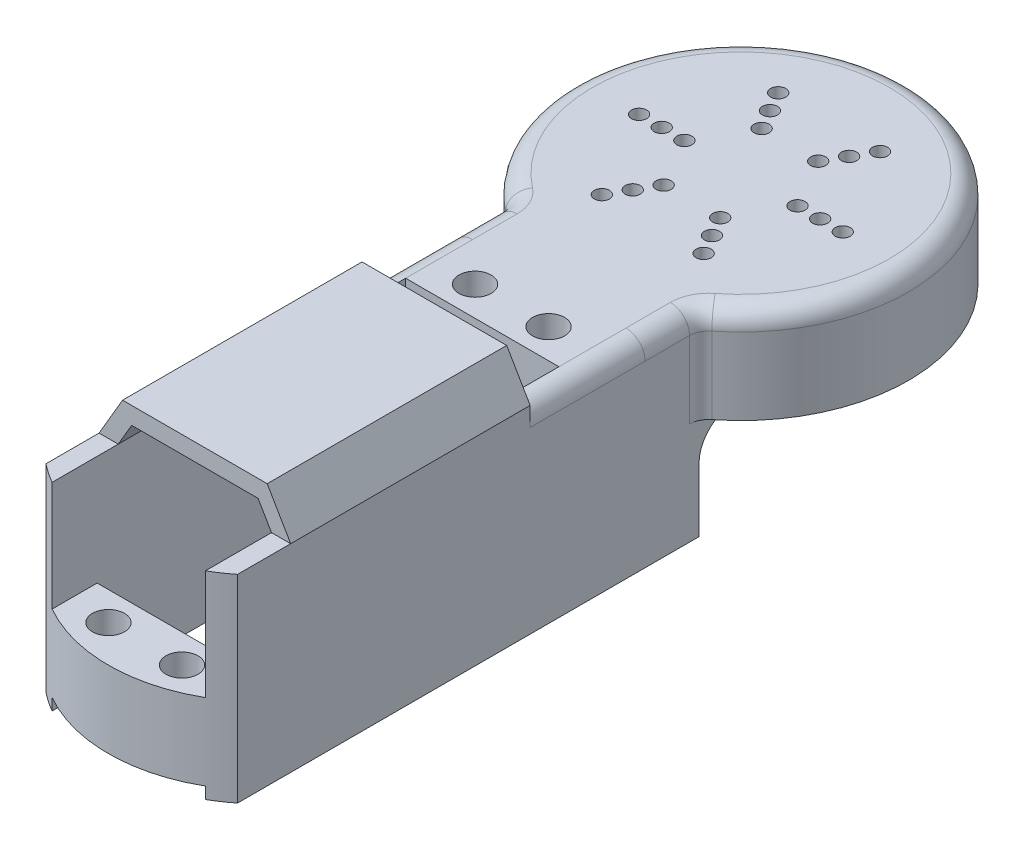
SolidWorks part; units mm, degrees
ref_plane "Front Plane" through (0, 0, 0) normal (0, 0, 1) x (1, 0, 0)
ref_plane "Top Plane" through (0, 0, 0) normal (0, 1, 0) x (1, 0, 0)
ref_plane "Right Plane" through (0, 0, 0) normal (1, 0, 0) x (0, 0, -1)
sketch "Sketch2" plane through (0, 0, 0) normal (0, 1, 0) x (1, 0, 0)
  circle A0 centre (0, 0) radius 22.225
  dimension "D1" = 44.45
extrude "Boss-Extrude1" add sketch "Sketch2" along normal blind 12.7
sketch "Sketch3" plane through (0, 12.7, 0) normal (0, 1, 0) x (1, 0, 0)
  circle A0 centre (-6.75, -11.6913) radius 1 construction
  circle A1 centre (-5.25, -9.0933) radius 1 construction
  circle A2 centre (-3.75, -6.4952) radius 1 construction
  circle A3 centre (-13.5, 0) radius 1 construction
  circle A4 centre (-10.5, 0) radius 1 construction
  circle A5 centre (-7.5, 0) radius 1 construction
  circle A6 centre (-3.75, 6.4952) radius 1 construction
  circle A7 centre (-5.25, 9.0933) radius 1 construction
  circle A8 centre (-6.75, 11.6913) radius 1 construction
  circle A9 centre (6.75, 11.6913) radius 1 construction
  circle A10 centre (5.25, 9.0933) radius 1 construction
  circle A11 centre (3.75, 6.4952) radius 1 construction
  circle A12 centre (13.5, 0) radius 1 construction
  circle A13 centre (10.5, 0) radius 1 construction
  circle A14 centre (7.5, 0) radius 1 construction
  circle A15 centre (3.75, -6.4952) radius 1 construction
  circle A16 centre (5.25, -9.0933) radius 1 construction
  circle A17 centre (6.75, -11.6913) radius 1 construction
  circle A18 centre (-6.75, -11.6913) radius 1
  circle A19 centre (-5.25, -9.0933) radius 1
  circle A20 centre (-3.75, -6.4952) radius 1
  circle A21 centre (-13.5, 0) radius 1
  circle A22 centre (-10.5, 0) radius 1
  circle A23 centre (-7.5, 0) radius 1
  circle A24 centre (-3.75, 6.4952) radius 1
  circle A25 centre (-5.25, 9.0933) radius 1
  circle A26 centre (-6.75, 11.6913) radius 1
  circle A27 centre (6.75, 11.6913) radius 1
  circle A28 centre (5.25, 9.0933) radius 1
  circle A29 centre (3.75, 6.4952) radius 1
  circle A30 centre (13.5, 0) radius 1
  circle A31 centre (10.5, 0) radius 1
  circle A32 centre (7.5, 0) radius 1
  circle A33 centre (3.75, -6.4952) radius 1
  circle A34 centre (5.25, -9.0933) radius 1
  circle A35 centre (6.75, -11.6913) radius 1
extrude "Cut-Extrude1" cut sketch "Sketch3" against normal through all
sketch "Sketch4" plane through (0, 12.7, 0) normal (0, 1, 0) x (1, 0, 0)
  line L3 (-12.7, -18.239) -> (-12.7, -25.4)
  line L4 (-12.7, -25.4) -> (12.7, -25.4)
  line L5 (12.7, -25.4) -> (12.7, -18.239)
  circle A2 centre (0, 0) radius 22.225
  arc A4 (-12.7, -18.239) -> (12.7, -18.239) centre (0, 0) ccw
  point P5 (0, 0)
  dimension "D2" = 25.4
  dimension "D3" = 25.4
  dimension "D1" = 0
extrude "Boss-Extrude2" add sketch "Sketch4" against normal blind 19.05
sketch "Sketch5" plane through (0, 12.7, 0) normal (0, 1, 0) x (1, 0, 0)
  line L3 (-12.7, -18.239) -> (-12.7, -25.4)
  line L4 (-12.7, -25.4) -> (12.7, -25.4)
  line L5 (12.7, -25.4) -> (12.7, -18.239)
  line L6 (-12.7, -18.239) -> (-12.7, -25.4)
  line L7 (-12.7, -25.4) -> (12.7, -25.4)
  line L8 (12.7, -25.4) -> (12.7, -18.239)
  arc A1 (12.7, -18.239) -> (-12.7, -18.239) centre (0, 0) ccw
  arc A2 (12.7, -18.239) -> (-12.7, -18.239) centre (0, 0) ccw
  point P0 (0, 0)
  dimension "D1" = 0
sketch "Sketch8" plane through (0, 0, 0) normal (0, -1, 0) x (1, 0, 0)
  circle A0 centre (0, 0) radius 17.78
  dimension "D1" = 35.56
extrude "Cut-Extrude2" cut sketch "Sketch8" against normal blind 5.08 contours A0
fillet "Fillet5" radius 5.08 1 edges at (0, 0, 22.225)
fillet "Fillet6" radius 2.54 2 edges at (12.7, 6.35, 18.239) (-12.7, 6.35, 18.239)
fillet "Fillet7" radius 2.54 5 edges at (-12.7, 12.7, 22.4602) (-12.9573, 12.7, 18.4066) (0, 12.7, -22.225) (12.9573, 12.7, 18.4066) (12.7, 12.7, 22.4602)
sketch "Sketch9" plane through (0, -6.35, 0) normal (0, -1, 0) x (1, 0, 0)
  line L3 (12.7, 18.239) -> (12.7, 25.4)
  line L4 (12.7, 25.4) -> (-12.7, 25.4)
  line L5 (-12.7, 25.4) -> (-12.7, 18.239)
  line L6 (12.7, 18.239) -> (12.7, 25.4)
  line L7 (12.7, 25.4) -> (-12.7, 25.4)
  line L8 (-12.7, 25.4) -> (-12.7, 18.239)
  arc A1 (12.7, 18.239) -> (-12.7, 18.239) centre (0, 0) ccw
  arc A2 (12.7, 18.239) -> (-12.7, 18.239) centre (0, 0) ccw
  dimension "D1" = 0
extrude "Boss-Extrude3" add sketch "Sketch9" along normal blind 7.2111
sketch "Sketch10" plane through (12.7, 0, 0) normal (1, 0, 0) x (0, 0, -1)
  line L0 (-25.4, 12.7) -> (-38.1, -0.8611)
  line L2 (-38.1, -0.8611) -> (-38.1, -13.5611)
  line L3 (-38.1, -13.5611) -> (-25.4, -13.5611)
  line L4 (-25.4, -13.5611) -> (-25.4, 12.7)
  point P3 (0, 0)
  point P8 (-34.1231, -0.7309)
  point P10 (-33.0317, -0.8508)
  point P11 (0, 0)
  dimension "D1" = 38.1
  dimension "D2" = 12.7
extrude "Boss-Extrude4" add sketch "Sketch10" against normal up to vertex (25.4 mm away) up to point (-12.7, -13.5611, 25.4)
ref_axis "Axis1" through (0, 27.5459, 0) along (0, -1, 0)
sketch "Sketch13" plane through (0, 0, 38.1) normal (0, 0, 1) x (1, 0, 0)
  line L1 (-12.7, -13.5611) -> (12.7, -13.5611)
  line L2 (-12.7, -13.5611) -> (-12.7, 12.7)
  line L3 (-12.7, 12.7) -> (12.7, 12.7)
  line L4 (12.7, -13.5611) -> (12.7, 12.7)
  point P6 (0, 0)
extrude "Boss-Extrude5" add sketch "Sketch13" against normal up to vertex (12.7 mm away) up to point (-12.7, 12.7, 25.4)
sketch "Sketch15" plane through (0, 12.7, 0) normal (0, 1, 0) x (1, 0, 0)
  line L0 (12.7, -38.1) -> (-12.7, -38.1) construction
  line L1 (-10.16, -38.1) -> (10.16, -38.1)
  line L2 (-10.16, -38.1) -> (-10.16, -34.29)
  line L3 (-10.16, -34.29) -> (10.16, -34.29)
  line L4 (10.16, -38.1) -> (10.16, -34.29)
  point P6 (0, -38.1)
  dimension "D1" = 3.81
  dimension "D2" = 20.32
extrude "Cut-Extrude3" cut sketch "Sketch15" against normal blind 58.7731
sketch "Sketch16" plane through (0, -13.5611, 0) normal (0, -1, 0) x (1, 0, 0)
  line L0 (-10.16, 34.29) -> (10.16, 34.29) construction
  line L1 (-10.16, 34.29) -> (10.16, 34.29)
  line L2 (-10.16, 34.29) -> (-10.16, 26.67)
  line L3 (-10.16, 26.67) -> (10.16, 26.67)
  line L4 (10.16, 34.29) -> (10.16, 26.67)
  point P6 (0, 26.67)
  dimension "D1" = 7.62
  dimension "D2" = 20.32
extrude "Cut-Extrude4" cut sketch "Sketch16" against normal blind 1.5494
sketch "Sketch18" plane through (0, -12.0117, 0) normal (0, -1, 0) x (1, 0, 0)
  line L1 (-10.16, 34.29) -> (-10.16, 26.67) construction
  line L2 (10.16, 26.67) -> (10.16, 38.1) construction
  line L3 (-10.16, 26.67) -> (10.16, 26.67) construction
  circle A0 centre (-4.8743, 30.3759) radius 2.126
  circle A1 centre (4.8743, 30.3759) radius 2.126
  point P4 (0, 0)
  point P5 (0, 0)
  dimension "D4" = 4.252
  dimension "D1" = 3.7059
  dimension "D2" = 5.2857
  dimension "D3" = 5.2857
extrude "Cut-Extrude5" cut sketch "Sketch18" against normal blind 38.1
sketch "Sketch19" plane through (0, 0, 38.1) normal (0, 0, 1) x (1, 0, 0)
  line L4 (-10.16, -13.5611) -> (-10.16, 12.7)
  line L5 (-10.16, 12.7) -> (-12.7, 12.7)
  line L6 (-12.7, 12.7) -> (-12.7, -13.5611)
  line L7 (-12.7, -13.5611) -> (-10.16, -13.5611)
  line L8 (-10.16, -13.5611) -> (-10.16, 12.7)
  line L9 (-10.16, 12.7) -> (-12.7, 12.7)
  line L10 (-12.7, 12.7) -> (-12.7, -13.5611)
  line L11 (-12.7, -13.5611) -> (-10.16, -13.5611)
  line L12 (10.16, 12.7) -> (10.16, -13.5611)
  line L13 (10.16, -13.5611) -> (12.7, -13.5611)
  line L14 (12.7, -13.5611) -> (12.7, 12.7)
  line L15 (12.7, 12.7) -> (10.16, 12.7)
  line L16 (10.16, 12.7) -> (10.16, -13.5611)
  line L17 (10.16, -13.5611) -> (12.7, -13.5611)
  line L18 (12.7, -13.5611) -> (12.7, 12.7)
  line L19 (12.7, 12.7) -> (10.16, 12.7)
  dimension "D1" = 0
  dimension "D2" = 0
extrude "Boss-Extrude6" add sketch "Sketch19" along normal blind 39.37
ref_plane "Plane1" through (0, 0, 40.64) normal (0, 0, 1) x (1, 0, 0)
sketch "Sketch20" plane through (0, 0, 40.64) normal (0, 0, 1) x (1, 0, 0)
  line L0 (-12.7, 12.7) -> (-9.5885, 18.034)
  line L1 (-9.5885, 18.034) -> (9.5885, 18.034)
  line L2 (9.5885, 18.034) -> (12.7, 12.7)
  line L3 (12.7, 12.7) -> (10.16, 12.7)
  line L4 (10.16, 12.7) -> (8.382, 15.748)
  line L5 (8.382, 15.748) -> (-8.382, 15.748)
  line L6 (-8.382, 15.748) -> (-10.16, 12.7)
  line L7 (-12.7, 12.7) -> (12.7, 12.7) construction
  line L8 (-12.7, 12.7) -> (-10.16, 12.7)
  dimension "D1" = 3.048
  dimension "D2" = 2.286
  dimension "D3" = 1.778
  dimension "D4" = 1.778
extrude "Boss-Extrude7" add sketch "Sketch20" along normal blind 31.75
fillet "Fillet12" radius 2.54 1 edges at (12.7, 12.7, 33.02) tangent propagation no
fillet "Fillet13" radius 2.54 1 edges at (-12.7, 12.7, 33.02) tangent propagation no
sketch "Sketch22" plane through (0, -13.5611, 0) normal (0, -1, 0) x (1, 0, 0)
  line L0 (-10.16, 77.47) -> (0, 63.5) construction
  circle A0 centre (0, 63.5) radius 20.3708 construction
  dimension "D3" = 40.7416
  dimension "D1" = 10.16
  dimension "D2" = 13.97
sketch "Sketch23" plane through (0, -13.5611, 0) normal (0, -1, 0) x (1, 0, 0)
  line L0 (-10.16, 77.47) -> (-10.16, 26.67) construction
  line L1 (-10.16, 75.184) -> (10.16, 75.184)
  line L2 (-10.16, 75.184) -> (-10.16, 81.1563)
  line L4 (10.16, 75.184) -> (10.16, 81.1563)
  line L5 (10.16, 34.29) -> (-10.16, 34.29) construction
  line L6 (10.16, 26.67) -> (10.16, 77.47) construction
  circle A0 centre (0, 63.5) radius 20.3708 construction
  arc A1 (-10.16, 81.1563) -> (10.16, 81.1563) centre (0, 63.5) cw
  point P13 (10.16, 75.184)
  dimension "D1" = 40.894
sketch "Sketch24" plane through (0, -12.0117, 0) normal (0, -1, 0) x (1, 0, 0)
  line L0 (-10.16, 75.184) -> (-10.16, 81.1563) construction
  line L1 (-10.16, 75.184) -> (10.16, 75.184) construction
  line L2 (-10.16, 75.184) -> (-10.16, 81.1563)
  line L3 (-10.16, 75.184) -> (10.16, 75.184)
  line L12 (10.16, 75.184) -> (10.16, 81.1563) construction
  line L13 (10.16, 75.184) -> (10.16, 81.1563)
  circle A0 centre (0, 63.5) radius 20.3708 construction
  arc A1 (10.16, 81.1563) -> (-10.16, 81.1563) centre (0, 63.5) ccw
extrude "Boss-Extrude8" add sketch "Sketch24" against normal blind 10.16
sketch "Sketch25" plane through (0, -12.0117, 0) normal (0, -1, 0) x (1, 0, 0)
  circle A0 centre (-4.8743, 78.9762) radius 2.126
  circle A1 centre (4.8743, 78.9762) radius 2.126
  circle A2 centre (-4.8743, 30.3759) radius 2.126 construction
  circle A3 centre (4.8743, 30.3759) radius 2.126 construction
  point P4 (0, 0)
  point P5 (4.2256, 77.4208)
  point P8 (0, 0)
  point P9 (0, 0)
  dimension "D1" = 48.6004
  dimension "D2" = 0
  dimension "D3" = 0
extrude "Cut-Extrude6" cut sketch "Sketch25" against normal blind 10.16
sketch "Sketch26" plane through (0, -13.5611, 0) normal (0, -1, 0) x (1, 0, 0)
  line L0 (-10.16, 81.1563) -> (-10.16, 77.47)
  line L1 (-10.16, 77.47) -> (-12.7, 77.47)
  line L2 (-12.7, 77.47) -> (-12.7, 79.4273)
  line L3 (10.16, 81.1563) -> (10.16, 77.47)
  line L4 (10.16, 77.47) -> (12.7, 77.47)
  line L5 (12.7, 77.47) -> (12.7, 79.4273)
  circle A0 centre (0, 63.5) radius 20.3708 construction
  arc A2 (-12.7, 79.4273) -> (-10.16, 81.1563) centre (0, 63.5) cw
  arc A3 (12.7, 79.4273) -> (10.143, 81.166) centre (0, 63.5) ccw
  line M7 (-10.16, 77.47) -> (-12.7, 77.47)
  line M11 (12.7, 77.47) -> (10.16, 77.47)
extrude "Boss-Extrude9" add sketch "Sketch26" against normal up to surface (26.2611 mm away) contours A2 L2 L0 M7 | L5 A3 L3 M11 region at (-11.3026, -13.5611, 78.9476) region at (11.3026, -13.5611, 78.9476) up to face at (0, 12.7, 19.2251)
